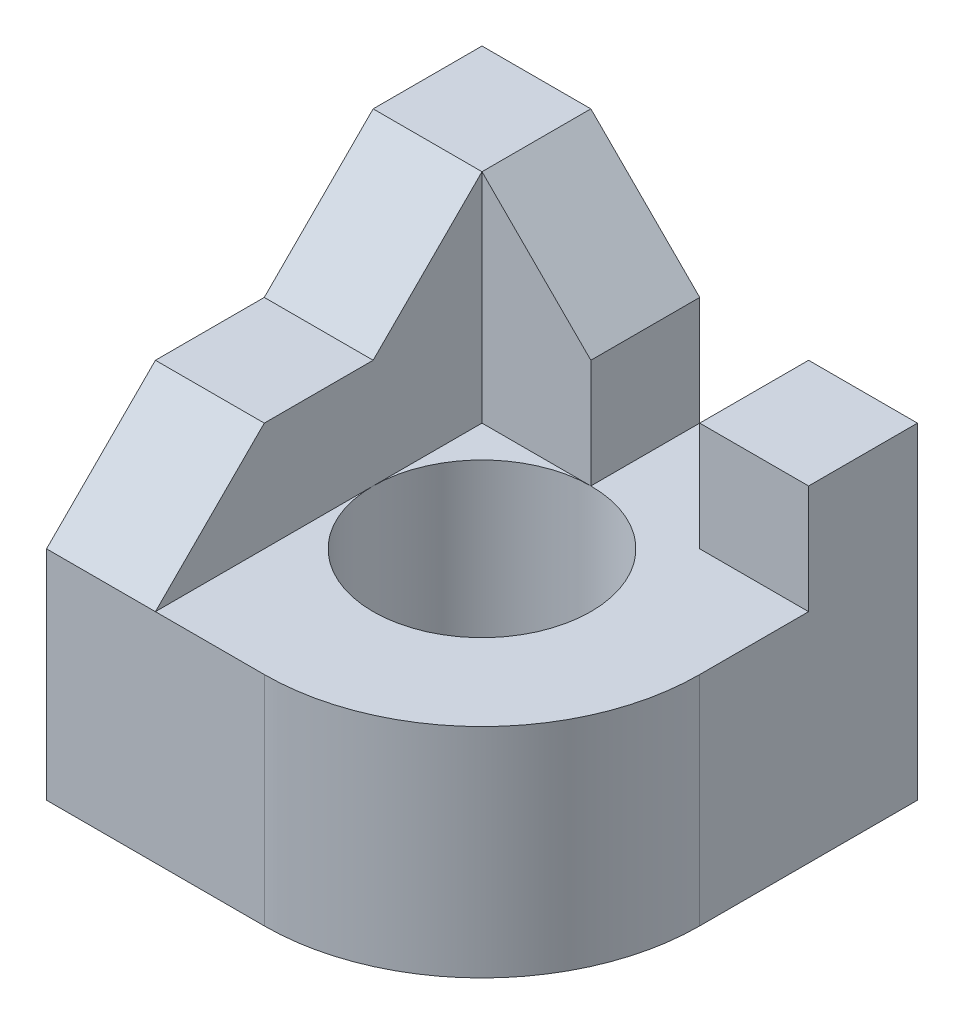
SolidWorks part; units mm, degrees
ref_plane "前基準面" through (0, 0, 0) normal (0, 0, 1) x (1, 0, 0)
ref_plane "上基準面" through (0, 0, 0) normal (0, 1, 0) x (1, 0, 0)
ref_plane "右基準面" through (0, 0, 0) normal (1, 0, 0) x (0, 0, -1)
sketch "草圖1" plane through (0, 0, 0) normal (0, 1, 0) x (1, 0, 0)
  line L0 (-2, 1) -> (0, 1)
  line L1 (2, 2) -> (-2, 2)
  line L2 (2, 2) -> (2, 0)
  line L3 (0, -2) -> (-2, -2)
  line L4 (-2, 2) -> (-2, -2)
  line L5 (2, 2) -> (-2, -2) construction
  line L6 (2, -2) -> (-2, 2) construction
  line L7 (-2, 2) -> (-1, 2)
  line L8 (-2, 2) -> (-2, -2)
  line L9 (-2, -2) -> (-1, -2)
  line L10 (-1, 2) -> (-1, -2)
  line L11 (0, 1) -> (0, 2)
  line L12 (-1, 0) -> (-2, 0)
  line L13 (-1, -1) -> (-2, -1)
  line L14 (1, 2) -> (1, 1)
  line L15 (1, 1) -> (2, 1)
  arc A0 (2, 0) -> (0, -2) centre (0, 0) cw
  circle A1 centre (0, 0) radius 1
  point P0 (0, 0)
  dimension "D3" = 2
  dimension "D4" = 2
  dimension "D1" = 4
  dimension "D2" = 4
  dimension "D5" = 1
  dimension "D6" = 1
  dimension "D7" = 1
  dimension "D8" = 1
extrude "填料-伸長1" add sketch "草圖1" along normal blind 2 contours A1 L10 L3 A0 L2 L15 L14 L1 L11 | A1 L0 L10 region at (-0.7766, 0, -0.7766) region at (0.05, 0, -1.5)
extrude "填料-伸長2" add sketch "草圖1<3>" along normal blind 3 contours L14 L15 L2 L1 | L10 L13 L4 L3 | L13 L10 L12 L8 region at (-1.5, 0, 0.5) region at (-1.5, 0, 1.5) region at (1.5, 0, -1.5)
sketch "草圖1<3>" plane through (0, 0, 0) normal (0, 1, 0) x (1, 0, 0) same geometry as "草圖1"
extrude "填料-伸長3" add sketch "草圖1<4>" along normal blind 4 contours L0 L11 L1 L10 | L10 L1 L4 L0 | L12 L10 L0 L4 region at (-1.5, 0, -1.5) region at (-1.5, 0, -0.5) region at (-0.5, 0, -1.5)
sketch "草圖1<4>" plane through (0, 0, 0) normal (0, 1, 0) x (1, 0, 0) same geometry as "草圖1"
chamfer "導角1" distance 1 angle 45 3 edges at (0, 4, -1.5) (-1.5, 4, 0) (-1.5, 3, 2)
